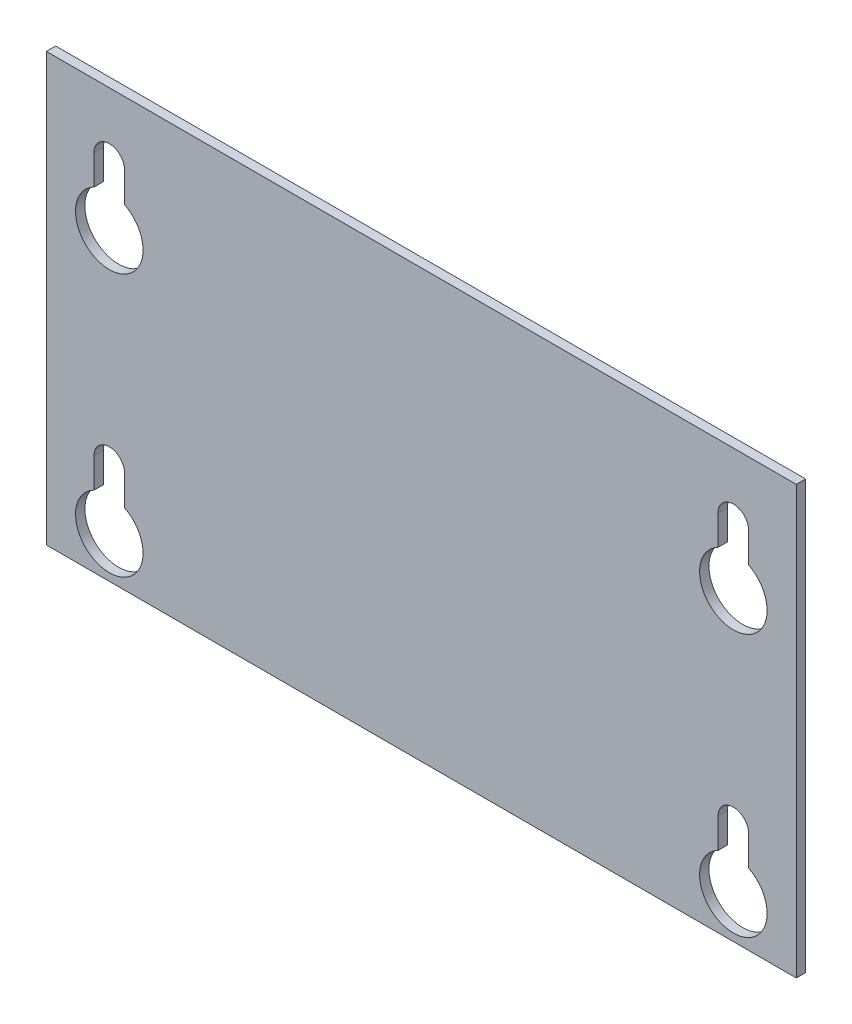
SolidWorks part; units mm, degrees
ref_plane "Front Plane" through (0, 0, 0) normal (0, 0, 1) x (1, 0, 0)
ref_plane "Top Plane" through (0, 0, 0) normal (0, 1, 0) x (1, 0, 0)
ref_plane "Right Plane" through (0, 0, 0) normal (1, 0, 0) x (0, 0, -1)
sketch "Sketch1" plane through (0, 0, 0) normal (0, 0, 1) x (1, 0, 0)
  line L1 (-50, 31) -> (50, 31)
  line L2 (-50, 31) -> (-50, -31)
  line L3 (-50, -31) -> (50, -31)
  line L4 (50, 31) -> (50, -31)
  line L5 (-50, 31) -> (50, -31) construction
  line L6 (-50, -31) -> (50, 31) construction
  point P0 (0, 0)
  dimension "D1" = 100
  dimension "D2" = 62
base flange "Base-Flange1" sketch "Sketch1" thickness 1.245 reverse thickness direction no parameters "D1"=1.71
sketch "Sketch6" plane through (0, 0, 0) normal (0, 0, 1) x (1, 0, 0)
  line L0 (-43.645, 17.5) -> (-43.645, 13.511)
  line L1 (-41.605, 17.5) -> (41.605, 17.5) construction
  line L2 (-41.605, 17.5) -> (-41.605, -17.5) construction
  line L3 (-41.605, -17.5) -> (41.605, -17.5) construction
  line L4 (41.605, 17.5) -> (41.605, -17.5) construction
  line L5 (-41.605, 17.5) -> (41.605, -17.5) construction
  line L6 (-41.605, -17.5) -> (41.605, 17.5) construction
  line L7 (-39.565, 17.5) -> (-39.565, 13.511)
  line L8 (39.565, 17.5) -> (39.565, 13.511)
  line L9 (43.645, 17.5) -> (43.645, 13.511)
  line L10 (-43.645, -17.5) -> (-43.645, -21.489)
  line L11 (-39.565, -17.5) -> (-39.565, -21.489)
  line L12 (39.565, -17.5) -> (39.565, -21.489)
  line L13 (43.645, -17.5) -> (43.645, -21.489)
  arc A0 (-39.565, 17.5) -> (-43.645, 17.5) centre (-41.605, 17.5) ccw
  arc A1 (43.645, 17.5) -> (39.565, 17.5) centre (41.605, 17.5) ccw
  arc A2 (43.645, -17.5) -> (39.565, -17.5) centre (41.605, -17.5) ccw
  arc A3 (-39.565, -17.5) -> (-43.645, -17.5) centre (-41.605, -17.5) ccw
  arc A4 (-43.645, 13.511) -> (-39.565, 13.511) centre (-41.605, 9.5) ccw
  arc A5 (39.565, 13.511) -> (43.645, 13.511) centre (41.605, 9.5) ccw
  arc A6 (-43.645, -21.489) -> (-39.565, -21.489) centre (-41.605, -25.5) ccw
  arc A7 (39.565, -21.489) -> (43.645, -21.489) centre (41.605, -25.5) ccw
  point P0 (0, 0)
  dimension "D3" = 4.08
  dimension "D4" = 9
  dimension "D5" = 8
  dimension "D6" = 8
  dimension "D1" = 83.21
  dimension "D2" = 35
extrude "Cut-Extrude7" cut sketch "Sketch6" against normal blind 10 normal cut yes
other "Move Face1" flip direction yes face at (0, 31, -0.6225) parameters "D1"=5
sketch "Bend-Lines1" plane through (0, 0, 0) normal (0, 1, 0) x (1, 0, 0)
sketch "Bounding-Box1" plane through (0, 0, 0) normal (0, 1, 0) x (1, 0, 0)
sheet metal parameters "Sheet-Metal1" thickness 1.245 parameters "D1"=1.71
flat pattern "Flat-Pattern1" [suppressed]
sketch "Bend-Lines2" plane through (0, 0, 0) normal (0, 1, 0) x (1, 0, 0)
sketch "Bounding-Box2" [suppressed] plane through (0, 0, 0) normal (0, 1, 0) x (1, 0, 0)
sheet metal parameters "Sheet-Metal2" thickness 1.245 parameters "D1"=1.71
flat pattern "Flat-Pattern1"
sketch "Bend-Lines2" plane through (0, 0, 0) normal (0, 1, 0) x (1, 0, 0)
sketch "Bounding-Box2" [suppressed] plane through (0, 0, 0) normal (0, 1, 0) x (1, 0, 0)
